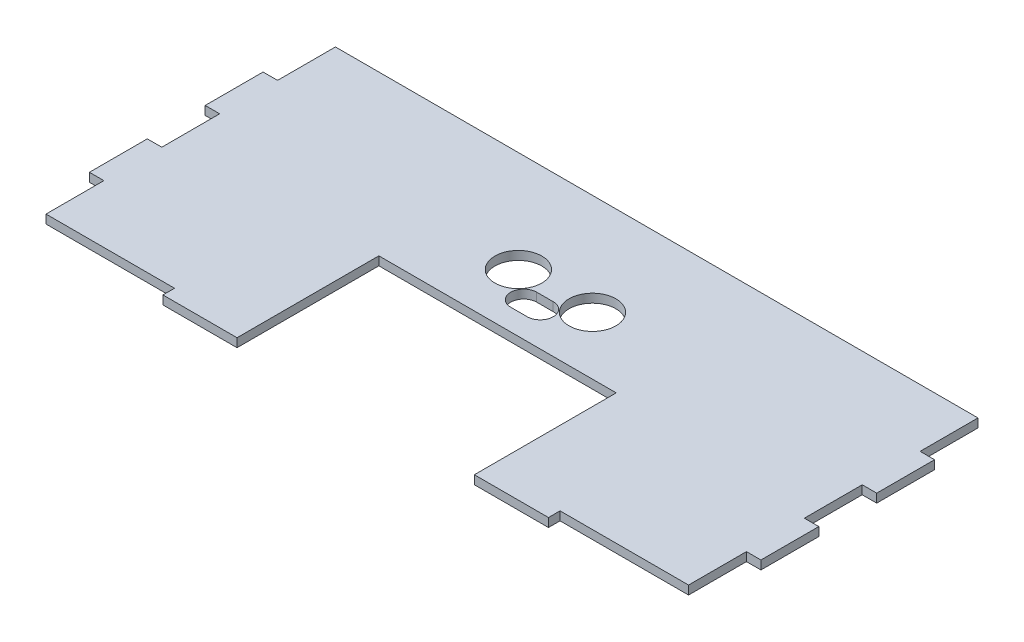
SolidWorks part; units mm, degrees
ref_plane "Front Plane" through (0, 0, 0) normal (0, 0, 1) x (1, 0, 0)
ref_plane "Top Plane" through (0, 0, 0) normal (0, 1, 0) x (1, 0, 0)
ref_plane "Right Plane" through (0, 0, 0) normal (1, 0, 0) x (0, 0, -1)
sketch "Sketch1" plane through (0, 0, 0) normal (0, 1, 0) x (1, 0, 0)
  line L0 (-111, 30) -> (-116, 30)
  line L1 (-111, -50) -> (-66.6, -50)
  line L2 (-111, -50) -> (-111, -30)
  line L3 (-111, 50) -> (111, 50)
  line L4 (111, -50) -> (111, -30)
  line L5 (-111, -50) -> (-41, -18.4685) construction
  line L6 (-111, 50) -> (11.1, -5) construction
  line L7 (-116, 30) -> (-116, 10)
  line L8 (-116, 10) -> (-111, 10)
  line L9 (0, 50) -> (0, 27.6) construction
  line L10 (-111, -10) -> (-116, -10)
  line L11 (-116, -10) -> (-116, -30)
  line L12 (-116, -30) -> (-111, -30)
  line L13 (-111, 30) -> (-111, 50)
  line L14 (-111, -10) -> (-111, 10)
  line L15 (116, -30) -> (111, -30)
  line L16 (116, -10) -> (116, -30)
  line L17 (111, -10) -> (116, -10)
  line L18 (116, 10) -> (111, 10)
  line L19 (116, 30) -> (116, 10)
  line L20 (111, 30) -> (116, 30)
  line L21 (111, 30) -> (111, 50)
  line L22 (111, -10) -> (111, 10)
  line L24 (-66.6, -54) -> (-41, -54)
  line L25 (-66.6, -54) -> (-66.6, -50)
  line L29 (66.6, -54) -> (66.6, -50)
  line L30 (41, -54) -> (66.6, -54)
  line L31 (66.6, -50) -> (111, -50)
  line L32 (-12.8, 15) -> (12.8, 15) construction
  line L35 (0, 18.6) -> (0, -5) construction
  line L36 (-2.85, 2.4) -> (2.85, 2.4)
  line L37 (-2.85, 11.4) -> (2.85, 11.4)
  line L38 (-11.1, -5) -> (111, 50) construction
  line L40 (-41, -54) -> (-41, -5)
  line L41 (-41, -5) -> (41, -5)
  line L42 (41, -54) -> (41, -5)
  line L45 (22.2, -54) -> (22.2, -50) [skipped]
  line L46 (41, -18.4685) -> (111, -50) construction
  circle A0 centre (12.8, 15) radius 8.1
  circle A1 centre (-12.8, 15) radius 8.1
  arc A4 (2.85, 11.4) -> (2.85, 2.4) centre (2.85, 6.9) cw
  arc A5 (-2.85, 2.4) -> (-2.85, 11.4) centre (-2.85, 6.9) cw
  point P0 (0, 0)
  dimension "D14" = 16.2
  dimension "D15" = 16.2
  dimension "D16" = 82
  dimension "D1" = 222
  dimension "D2" = 100
  dimension "D3" = 20
  dimension "D4" = 20
  dimension "D5" = 5
  dimension "D8" = 2
  dimension "D9" = 44.4
  dimension "D10" = 4
  dimension "D11" = 12.8
  dimension "D12" = 12.8
  dimension "D6" = 2
extrude "Boss-Extrude1" add sketch "Sketch1" along normal blind 3
